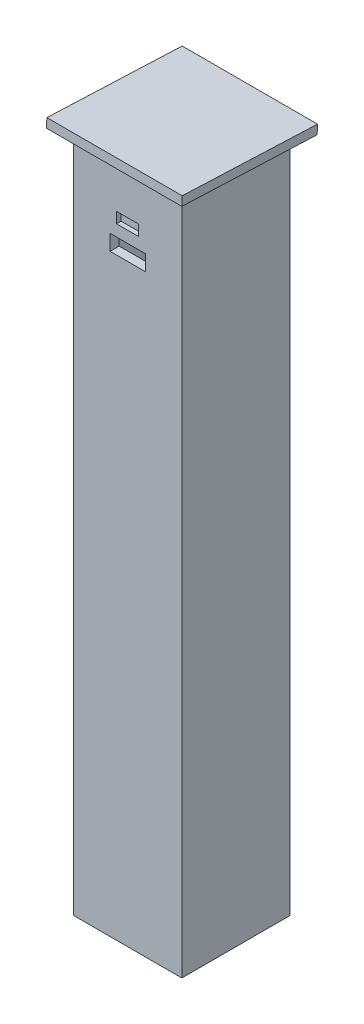
SolidWorks part; units mm, degrees
ref_plane "Спереди" through (0, 0, 0) normal (0, 0, 1) x (1, 0, 0)
ref_plane "Сверху" through (0, 0, 0) normal (0, 1, 0) x (1, 0, 0)
ref_plane "Справа" through (0, 0, 0) normal (1, 0, 0) x (0, 0, -1)
sketch "Эскиз1" plane through (0, 0, 0) normal (0, 1, 0) x (1, 0, 0)
  line L1 (-263.3228, 128.3516) -> (-63.3228, 128.3516)
  line L2 (-263.3228, 128.3516) -> (-263.3228, -71.6484)
  line L3 (-263.3228, -71.6484) -> (-63.3228, -71.6484)
  line L4 (-63.3228, 128.3516) -> (-63.3228, -71.6484)
  line L5 (-283.3228, 148.3516) -> (-43.3228, 148.3516)
  line L6 (-283.3228, 148.3516) -> (-283.3228, -91.6484)
  line L7 (-283.3228, -91.6484) -> (-43.3228, -91.6484)
  line L8 (-43.3228, 148.3516) -> (-43.3228, -91.6484)
  dimension "D1" = 200
  dimension "D2" = 200
  dimension "D3" = 20
  dimension "D4" = 20
  dimension "D5" = 20
  dimension "D6" = 20
extrude "Бобышка-Вытянуть1" add sketch "Эскиз1" along normal blind 1500
sketch "Эскиз2" plane through (0, 0, 91.6484) normal (0, 0, 1) x (1, 0, 0)
  line L0 (-163.3228, 1500) -> (-163.3228, -337.4363) construction
  line L1 (-283.3228, 1500) -> (-43.3228, 1500) construction
  line L3 (-202.3228, 1350) -> (-124.3228, 1350)
  line L4 (-202.3228, 1350) -> (-202.3228, 1315.5)
  line L5 (-202.3228, 1315.5) -> (-124.3228, 1315.5)
  line L6 (-124.3228, 1350) -> (-124.3228, 1315.5)
  point P8 (-163.3228, 1350)
  dimension "D1" = 34.5
  dimension "D2" = 78
  dimension "D3" = 150
extrude "Вырез-Вытянуть1" cut sketch "Эскиз2" against normal up to surface (20 mm away) up to face at (-163.3228, 750, 71.6484)
sketch "Эскиз3" plane through (-283.3228, 0, 0) normal (-1, 0, 0) x (0, 0, 1)
  line L0 (-148.3516, 1500) -> (91.6484, 1500)
  line L1 (91.6484, 1500) -> (91.6484, 1510)
  line L2 (91.6484, 1510) -> (-148.3516, 1500)
  dimension "D1" = 10
extrude "Бобышка-Вытянуть2" add sketch "Эскиз3" against normal up to surface (240 mm away) up to face at (-43.3228, 750, -28.3516)
sketch "Эскиз4" plane through (0, 1503.571, -62.6488) normal (0, 0.9991, -0.0416) x (1, 0, 0)
  line L0 (-43.3228, 85.7772) -> (-43.3228, -154.431) construction
  line L1 (-313.3228, 115.7772) -> (-13.3228, 115.7772)
  line L2 (-313.3228, 115.7772) -> (-313.3228, -184.431)
  line L3 (-313.3228, -184.431) -> (-13.3228, -184.431)
  line L4 (-13.3228, 115.7772) -> (-13.3228, -184.431)
  line L5 (-43.3228, -154.431) -> (-283.3228, -154.431) construction
  line L6 (-283.3228, -154.431) -> (-283.3228, 85.7772) construction
  line L7 (-43.3228, 85.7772) -> (-283.3228, 85.7772) construction
  dimension "D1" = 30
  dimension "D2" = 30
  dimension "D3" = 30
  dimension "D4" = 30
extrude "Бобышка-Вытянуть3" add sketch "Эскиз4" along normal blind 20
sketch "Эскиз5" plane through (0, 0, 91.6484) normal (0, 0, 1) x (1, 0, 0)
  line L8 (-163.3228, 1511.2489) -> (-163.3228, 1253.7199) construction
  line L9 (-187.8228, 1399.5) -> (-138.8228, 1399.5)
  line L10 (-187.8228, 1399.5) -> (-187.8228, 1375.5)
  line L11 (-187.8228, 1375.5) -> (-138.8228, 1375.5)
  line L23 (-138.8228, 1399.5) -> (-138.8228, 1375.5)
  line L24 (-313.3228, 1511.2489) -> (-13.3228, 1511.2489) construction
  line L25 (-124.3228, 1350) -> (-202.3228, 1350) construction
  point P8 (-163.3228, 1399.5)
  dimension "D2" = 24
  dimension "D3" = 25.5
  dimension "D1" = 49
sketch "Эскиз6" plane through (0, 0, 91.6484) normal (0, 0, 1) x (1, 0, 0)
  line L0 (-163.3228, 1510) -> (-163.3228, 1337.4959) construction
  line L1 (-43.3228, 1510) -> (-283.3228, 1510) construction
  line L2 (-124.3228, 1350) -> (-202.3228, 1350) construction
  line L3 (-187.8228, 1399.5) -> (-138.8228, 1399.5)
  line L4 (-187.8228, 1399.5) -> (-187.8228, 1375.5)
  line L5 (-187.8228, 1375.5) -> (-138.8228, 1375.5)
  line L6 (-138.8228, 1399.5) -> (-138.8228, 1375.5)
  point P10 (-163.3228, 1399.5)
  dimension "D1" = 49
  dimension "D2" = 24
  dimension "D3" = 25.5
extrude "Вырез-Вытянуть3" cut sketch "Эскиз6" against normal blind 10
ref_plane "Плоскость1" through (-163.3228, 0, 0) normal (1, 0, 0) x (0, 0, -1)
